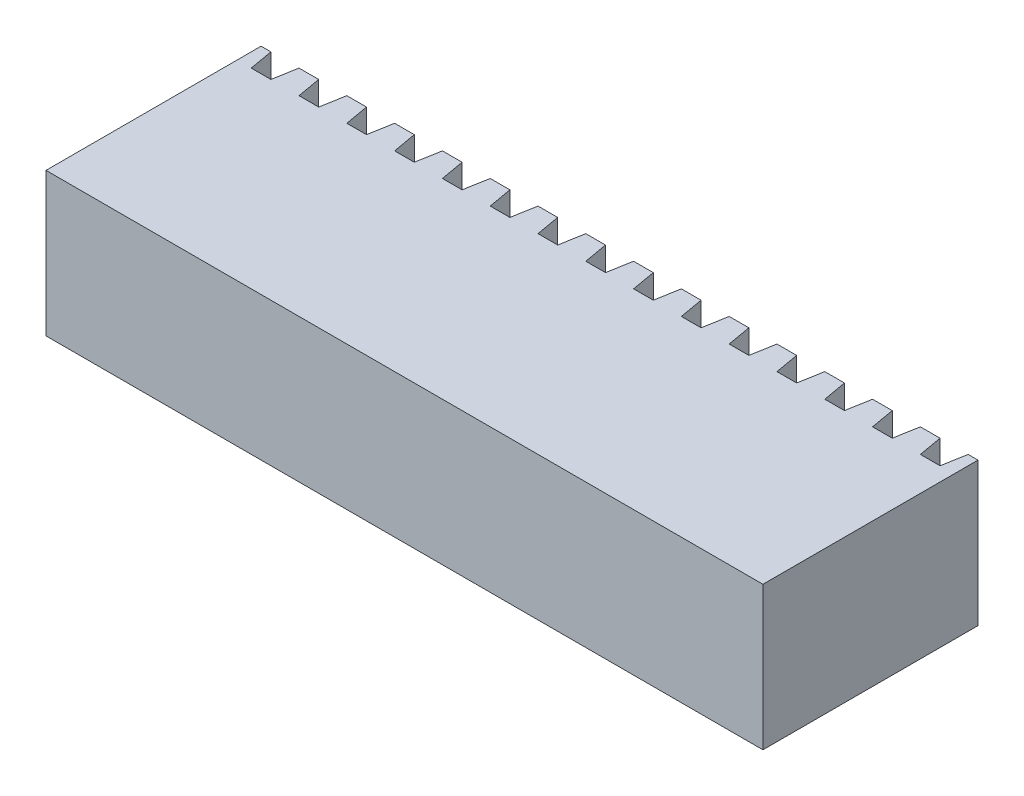
SolidWorks part; units mm, degrees
material "Maple"
ref_plane "Front Plane" through (0, 0, 0) normal (0, 0, 1) x (1, 0, 0)
ref_plane "Top Plane" through (0, 0, 0) normal (0, 1, 0) x (1, 0, 0)
ref_plane "Right Plane" through (0, 0, 0) normal (1, 0, 0) x (0, 0, -1)
sketch "Sketch1" plane through (0, 0, 0) normal (0, 1, 0) x (1, 0, 0)
  line L1 (0, 0) -> (30, 0)
  line L2 (0, 0) -> (0, 9)
  line L3 (0, 9) -> (30, 9)
  line L4 (30, 0) -> (30, 9)
  dimension "D1" = 30
  dimension "D2" = 9
extrude "Boss-Extrude1" add sketch "Sketch1" along normal blind 6
ref_plane "Plane1" through (0, 3, 0) normal (0, 1, 0) x (1, 0, 0)
ref_plane "Plane2" through (0, 0, -10) normal (0, 0, -1) x (-1, 0, 0)
sketch "Sketch2" plane through (0, 6, 0) normal (0, 1, 0) x (1, 0, 0)
  line L0 (15, 8) -> (15, 9) construction
  line L1 (14.4118, 9) -> (15.5882, 9)
  line L2 (14.4118, 9) -> (14.5882, 8)
  line L3 (14.5882, 8) -> (15.4118, 8)
  line L4 (15.4118, 8) -> (15.5882, 9)
  line L5 (14.5, 8.5) -> (15.5, 8.5) construction
  line L7 (30, 9) -> (0, 9) construction
  line L8 (0, 9) -> (0, 0) construction
  line L9 (30, 0) -> (30, 9) construction
  dimension "D1" = 10
  dimension "D2" = 1
  dimension "D3" = 1
extrude "Cut-Extrude1" cut sketch "Sketch2" against normal through all
pattern_linear "LPattern2" count 8 spacing 2 along (-1, 0, 0) count 8 spacing 2 along (1, 0, 0) of "Cut-Extrude1"
